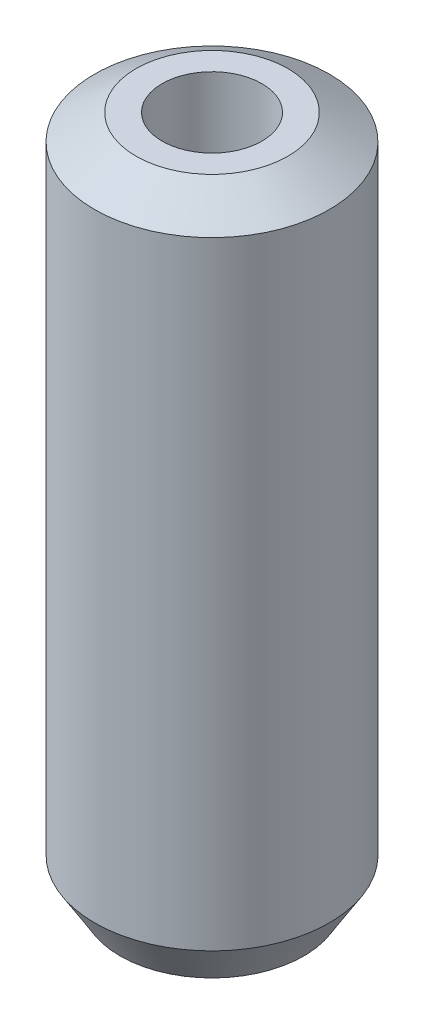
SolidWorks part; units mm, degrees
ref_plane "Front Plane" through (0, 0, 0) normal (0, 0, 1) x (1, 0, 0)
ref_plane "Top Plane" through (0, 0, 0) normal (0, 1, 0) x (1, 0, 0)
ref_plane "Right Plane" through (0, 0, 0) normal (1, 0, 0) x (0, 0, -1)
sketch "Sketch1" plane through (0, 0, 0) normal (0, 1, 0) x (1, 0, 0)
  circle A0 centre (0, 0) radius 5
  dimension "SHAFT_OD" = 10
extrude "Boss-Extrude1" add sketch "Sketch1" along normal blind 29.1641
sketch "Sketch2" plane through (0, 0, 0) normal (0, 1, 0) x (1, 0, 0)
  circle A0 centre (0, 0) radius 2.1245
  dimension "BORE_D" = 4.249
extrude "Cut-Extrude1" cut sketch "Sketch2" along normal through all
chamfer "Chamfer1" distance 1.0848 angle 58.43 2 edges at (0, 29.1641, 5) (0, 0, 5) first distance on face at (0, 29.1641, 5) first distance on face at (0, 0, 2.1245)
